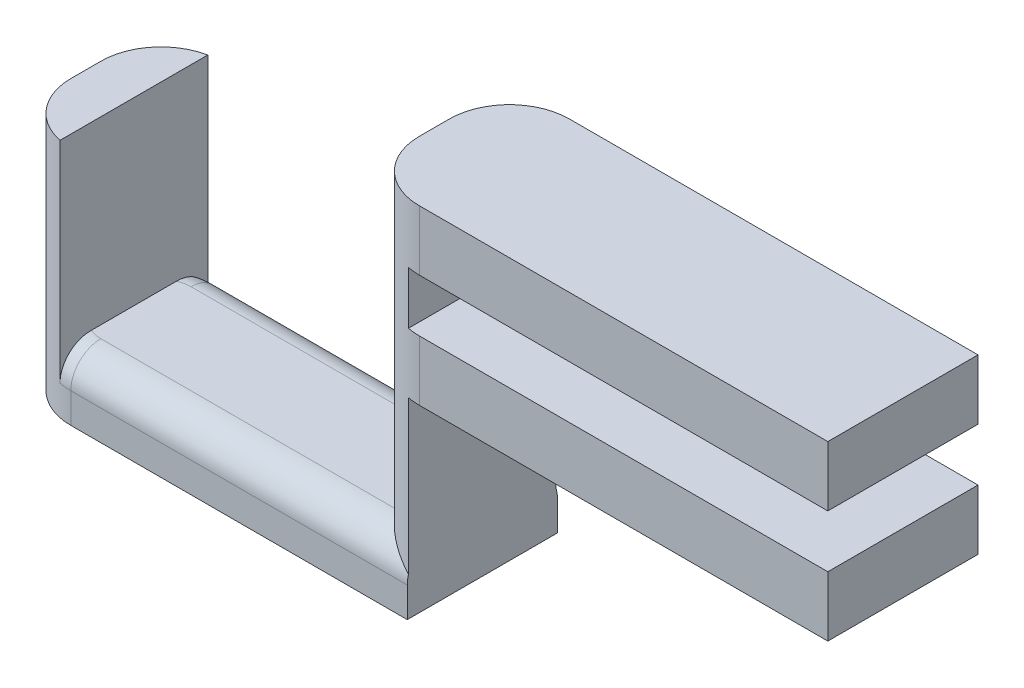
SolidWorks part; units mm, degrees
ref_plane "前基準面" through (0, 0, 0) normal (0, 0, 1) x (1, 0, 0)
ref_plane "上基準面" through (0, 0, 0) normal (0, 1, 0) x (1, 0, 0)
ref_plane "右基準面" through (0, 0, 0) normal (1, 0, 0) x (0, 0, -1)
sketch "草圖1" plane through (0, 0, 0) normal (0, 0, 1) x (1, 0, 0)
  line L0 (10.7062, 13.8844) -> (10.7062, 22.6478)
  line L2 (-55.2938, 11.9758) -> (-55.2938, -28.0242)
  line L4 (-47.2938, 11.9758) -> (-47.2938, -18.0242)
  line L5 (-47.2938, -18.0242) -> (2.7062, -18.0242)
  line L7 (-55.2938, -28.0242) -> (10.7062, -28.0242)
  line L10 (2.7062, -18.0242) -> (2.7062, 32.6478)
  line L12 (10.7062, -28.0242) -> (10.7062, 3.8844)
  line L13 (2.7062, 32.6478) -> (80.7062, 32.6478)
  line L15 (10.7062, 22.6478) -> (80.7062, 22.6478)
  line L16 (80.7062, 32.6478) -> (80.7062, 22.6478)
  line L17 (10.7062, 13.8844) -> (80.7062, 13.8844)
  line L19 (10.7062, 3.8844) -> (80.7062, 3.8844)
  line L20 (80.7062, 13.8844) -> (80.7062, 3.8844)
  line L21 (-55.2938, 11.9758) -> (-47.2938, 11.9758)
  dimension "D1" = 50
  dimension "D2" = 8
  dimension "D3" = 10
  dimension "D4" = 8
  dimension "D5" = 10
  dimension "D6" = 10
  dimension "D7" = 30
  dimension "D8" = 40
  dimension "D9" = 70
  dimension "D10" = 70
extrude "填料-伸長1" add sketch "草圖1" along normal blind 25
fillet "圓角2" radius 10 1 edges at (-55.2938, -8.0242, 0)
fillet "圓角3" radius 10 1 edges at (-55.2938, -8.0242, 25)
fillet "圓角4" radius 10 2 edges at (2.7062, 7.3118, 25) (2.7062, 7.3118, 0)
fillet "圓角6" radius 5 4 edges at (-46.2989, -18.0242, 24.9494) (-46.2989, -18.0242, 0.0506) (-17.2938, -18.0242, 25) (-17.2938, -18.0242, 0)
